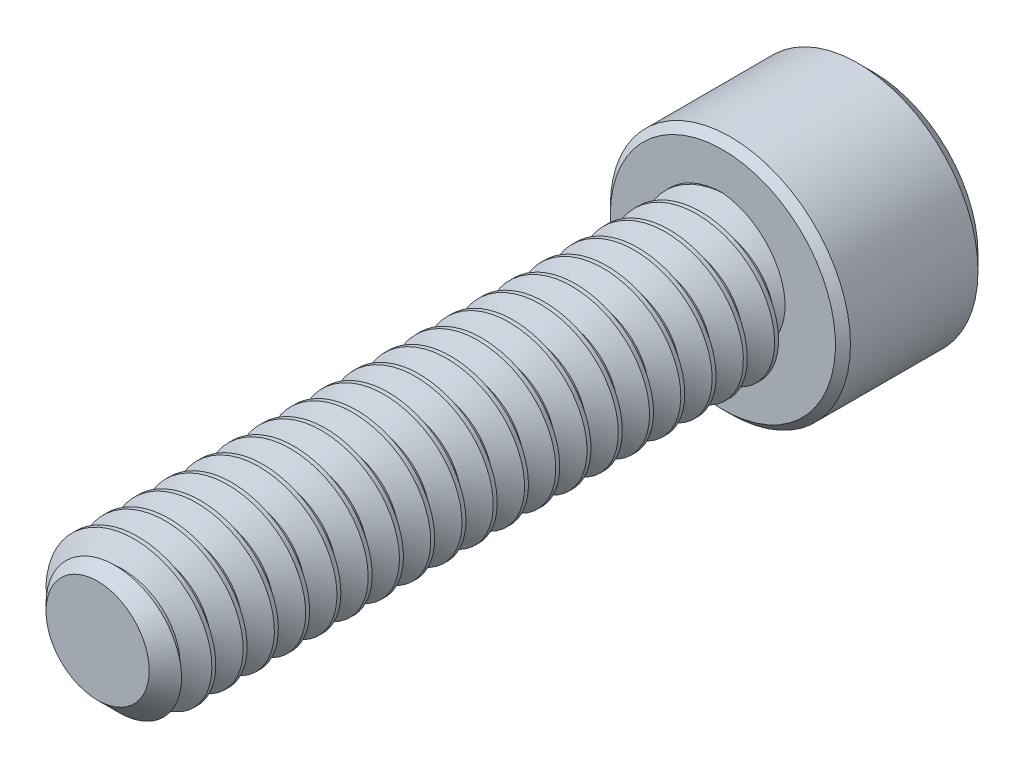
SolidWorks part; units mm, degrees
ref_plane "Front Plane" through (0, 0, 0) normal (0, 0, 1) x (1, 0, 0)
ref_plane "Top Plane" through (0, 0, 0) normal (0, 1, 0) x (1, 0, 0)
ref_plane "Right Plane" through (0, 0, 0) normal (1, 0, 0) x (0, 0, -1)
sketch "Sketch1" plane through (0, 0, 0) normal (0, 0, 1) x (1, 0, 0)
  line L0 (0, 0.762) -> (0, -0.762) construction
  circle A0 centre (0, 0) radius 0.762
  dimension "OD" = 1.524
extrude "Extrude1" add sketch "Sketch1" against normal blind 6.35
sketch "Sketch2" plane through (0, 0, 0) normal (0, 0, 1) x (1, 0, 0)
  circle A0 centre (0, 0) radius 0.762 construction
  circle A1 centre (0, 0) radius 0.762
curve "Helix/Spiral1" pitch 0.3175 height 6.6675 radius 0.762 centre (0, 0, 0) axis (0, 0, -1) start towards (0, 1, 0) parameters "pitch"=0.3175
chamfer "Chamfer3" distance 0.2381 angle 45 1 edges at (0.762, 0, 0)
sketch "Sketch3" plane through (0, 0, 0) normal (1, 0, 0) x (0, 0, -1)
  line L0 (-0.2778, 0.762) -> (-0.1588, 0.5558)
  line L1 (-0.1588, 0.5558) -> (-0.1191, 0.5558)
  line L2 (-0.1191, 0.5558) -> (0, 0.762)
  line L3 (-0.2778, 0.762) -> (0, 0.762)
  line L4 (-0.1389, 0.762) -> (-0.1389, 0.5558) construction
  line L5 (-0.2183, 0.6589) -> (-0.0595, 0.6589) construction
  line L6 (0, 0.762) -> (0, -0.762) construction
  dimension "D1" = 0.0397
  dimension "D2" = 0.1588
  dimension "D3" = 60
sweep "Cut-Sweep1" cut profiles "Sketch3" path "Helix/Spiral1" align with end faces yes
sketch "Sketch6" plane through (0, 0, -6.35) normal (0, 0, -1) x (-1, 0, 0)
  circle A0 centre (0, 0) radius 1.2192
  dimension "head dia" = 2.4384
extrude "Extrude2" add sketch "Sketch6" along normal blind 1.524
sketch "Sketch7" plane through (0, 0, -7.874) normal (0, 0, -1) x (-1, 0, 0)
  line L1 (0, 0.7332) -> (-0.635, 0.3666)
  line L2 (-0.635, 0.3666) -> (-0.635, -0.3666)
  line L3 (-0.635, -0.3666) -> (0, -0.7332)
  line L4 (0, -0.7332) -> (0.635, -0.3666)
  line L5 (0.635, -0.3666) -> (0.635, 0.3666)
  line L6 (0.635, 0.3666) -> (0, 0.7332)
  circle A0 centre (0, 0) radius 0.635 construction
  dimension "hex dia" = 1.27
extrude "Cut-Extrude1" cut sketch "Sketch7" against normal blind 0.9525
sketch "Sketch8" plane through (0, 0, -7.874) normal (0, 0, -1) x (-1, 0, 0)
  circle A0 centre (0, 0) radius 0.7332
extrude "Cut-Extrude2" cut sketch "Sketch8" against normal blind 0.1524 draft 45
chamfer "Chamfer1" distance 0.1524 angle 45 1 edges at (-1.2192, 0, -7.874)
chamfer "Chamfer2" distance 0.0762 angle 45 1 edges at (-1.2192, 0, -6.35)
sketch "Sketch9" plane through (0, 0, 0) normal (1, 0, 0) x (0, 0, -1)
  line L0 (0, 0.762) -> (0, -0.762) construction
  line L1 (1.7463, 0.762) -> (1.7463, -0.762) construction
  line L2 (6.35, 1.2192) -> (6.35, -1.2192) construction
  line L3 (7.874, 1.2192) -> (7.874, -1.2192) construction
  line L4 (7.874, 0) -> (0, 0) construction
  dimension "D1" = 1.7463
  dimension "D2" = 1.524
  dimension "D3" = 2.4384
  dimension "D4" = 6.35
equation "\"D3@Helix/Spiral1\" = \"screw length@Extrude1\"+\"pitch@Helix/Spiral1\""
equation "\"D1@Sketch3\" = \"pitch@Helix/Spiral1\"*.125"
equation "\"D2@Sketch3\" = \"pitch@Helix/Spiral1\"*.5"
equation "\"D1@Cut-Extrude1\" = \"hex dia@Sketch7\"*.75"
equation "\"D1@Chamfer1\" = \"head depth@Extrude2\"/10"
equation "\"D1@Sketch9\" = \"pitch@Helix/Spiral1\"*5.5"
equation "\"D1@Chamfer2\" = \"D1@Chamfer1\"/2"
equation "\"D1@Cut-Extrude2\" = \"D1@Chamfer2\"*2"
equation "\"D1@Chamfer3\" = \"pitch@Helix/Spiral1\"*.750"
equation "\"D2@Sketch9\" = \"head depth@Extrude2\""
equation "\"D3@Sketch9\" = \"head dia@Sketch6\""
equation "\"D4@Sketch9\" = \"screw length@Extrude1\""
